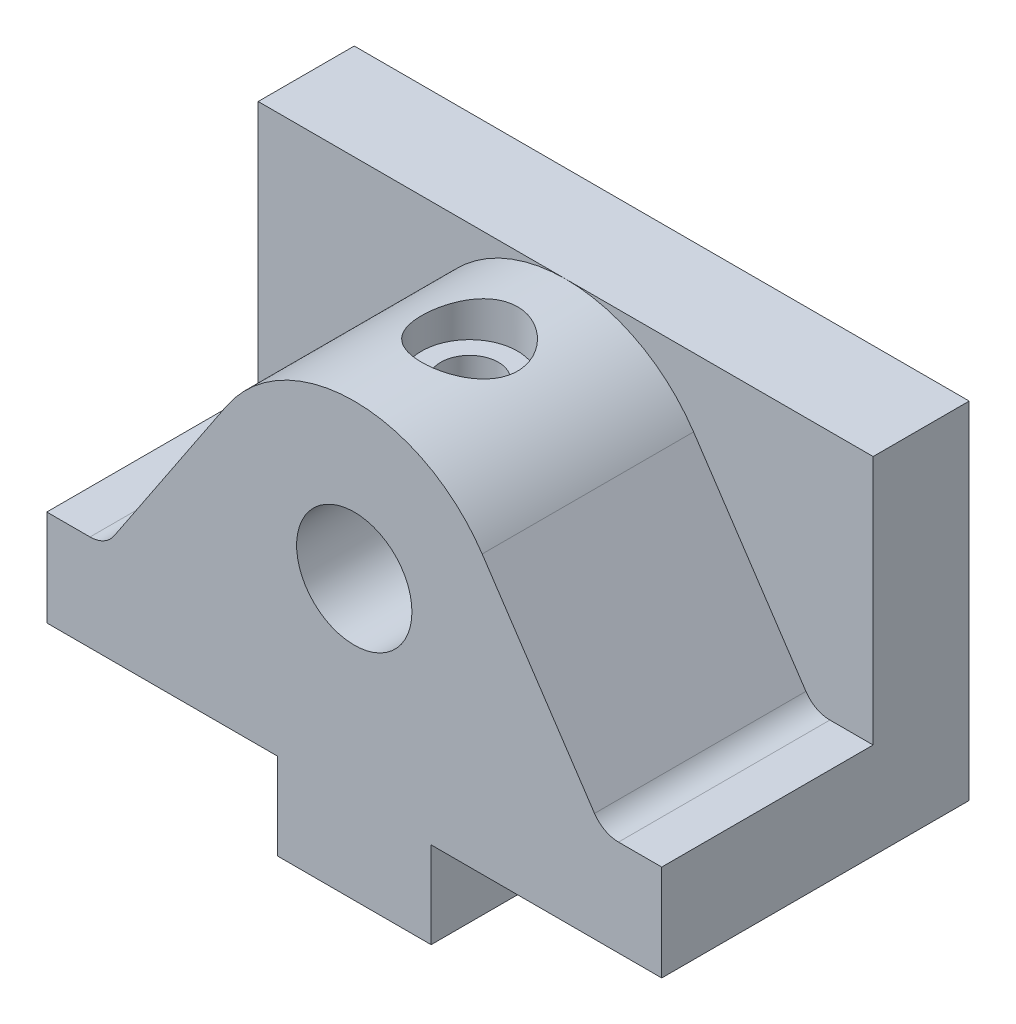
SolidWorks part; units mm, degrees
ref_plane "Front Plane" through (0, 0, 0) normal (0, 0, 1) x (1, 0, 0)
ref_plane "Top Plane" through (0, 0, 0) normal (0, 1, 0) x (1, 0, 0)
ref_plane "Right Plane" through (0, 0, 0) normal (1, 0, 0) x (0, 0, -1)
sketch "Sketch2" plane through (0, 0, 0) normal (0, 0, 1) x (1, 0, 0)
  line L0 (-32, 26) -> (32, 26) construction
  line L3 (0, 52) -> (0, 0) construction
  line L5 (-32, 16) -> (32, 16)
  line L6 (-8, 16) -> (-8, 7)
  line L7 (-8, 7) -> (8, 7)
  line L8 (-32, 0) -> (32, 0)
  line L9 (32, 0) -> (32, 52)
  line L10 (32, 52) -> (-32, 52)
  line L11 (-32, 52) -> (-32, 0)
  line L12 (-13.3134, 44.8742) -> (-25.0037, 27.3361)
  line L13 (-32, 26) -> (32, 26) construction
  line L14 (-32, 36) -> (32, 36) construction
  line L17 (8, 7) -> (8, 16)
  line L18 (13.3134, 44.8742) -> (25.0037, 27.3361)
  line L19 (-27.5, 26) -> (-32, 26)
  line L20 (27.5, 26) -> (32, 26)
  arc A1 (-13.3134, 44.8742) -> (13.3134, 44.8742) centre (0, 36) cw
  circle A3 centre (0, 36) radius 6
  arc A4 (-25.0037, 27.3361) -> (-27.5, 26) centre (-27.5, 29) cw
  arc A5 (25.0037, 27.3361) -> (27.5, 26) centre (27.5, 29) ccw
  point P30 (0, 26)
  dimension "D4" = 16
  dimension "D5" = 3
  dimension "D6" = 55
  dimension "D7" = 10
  dimension "D11" = 12
  dimension "D2" = 3
  dimension "D3" = 16
  dimension "D9" = 16
  dimension "D10" = 9
  dimension "D12" = 52
  dimension "D13" = 64
extrude "Boss-Extrude1" add sketch "Sketch2" along normal blind 22 contours A5 L18 A1 L12 A4 L19 L11 L5 L9 L20 A3 | L7 L17 L5 L6 region at (0, 29.4355, 0) region at (0, 11.5, 0)
extrude "Boss-Extrude2" add sketch "Sketch2<9>" against normal blind 10 contours L18 A5 L20 L9 L10 A1 | A5 L18 A1 L12 A4 L19 L11 L5 L9 L20 A3 | A4 L12 A1 L10 L11 L19 | A3 region at (0, 29.4355, 0) region at (-23.3107, 41.8121, 0) region at (23.3107, 41.8121, 0) region at (0, 36, 0)
sketch "Sketch2<9>" plane through (0, 0, 0) normal (0, 0, 1) x (1, 0, 0) same geometry as "Sketch2"
sketch "Sketch3" plane through (0, 0, 0) normal (0, 0, 1) x (1, 0, 0)
  circle A1 centre (0, 36) radius 6
  circle A2 centre (0, 36) radius 6
  dimension "D1" = 0
extrude "Cut-Extrude1" cut sketch "Sketch3" against normal blind 2 contours A2
sketch "Sketch5" plane through (0, 0, 0) normal (0, 0, -1) x (-1, 0, 0)
  line L4 (8, 7) -> (8, 16)
  line L5 (8, 16) -> (-8, 16)
  line L6 (-8, 16) -> (-8, 7)
  line L7 (-8, 7) -> (8, 7)
  line L8 (8, 7) -> (8, 16)
  line L9 (8, 16) -> (-8, 16)
  line L10 (-8, 16) -> (-8, 7)
  line L11 (-8, 7) -> (8, 7)
  dimension "D1" = 0
extrude "Boss-Extrude3" add sketch "Sketch5" along normal up to surface (10 mm away) up to face at (0, 34, -10)
sketch "Sketch4" plane through (0, 7, 0) normal (0, -1, 0) x (1, 0, 0)
  line L0 (0, 22) -> (0, -10) construction
  line L4 (-8, -10) -> (8, -10)
  line L5 (8, -10) -> (8, 22)
  line L6 (8, 22) -> (-8, 22)
  line L7 (-8, 22) -> (-8, -10)
  line L9 (8, -10) -> (8, 22)
  line L10 (8, 22) -> (-8, 22)
  line L11 (-8, 22) -> (-8, -10)
  line L12 (-8, -10) -> (8, -10)
  point P2 (0, 14)
  point P4 (0, -2)
  dimension "D2" = 8
  dimension "D3" = 16
  dimension "D1" = 0
hole_wizard "M6x1.0 Tapped Hole1" positions "3DSketch1" profile "Sketch6" tap size "M6x1.0" standard "ANSI Metric"
sketch3d "3DSketch1"
  line L0 (0, 7, 22) -> (0, 7, -10) construction
  point P0 (0, 7, 14)
  point P7 (0, 7, -2)
sketch "Sketch6" plane through (0, 7, 14) normal (1, 0, 0) x (0, 0, -1)
  line L0 (0, 0) -> (0, 17.7321)
  line L1 (0, 17.7321) -> (3, 16)
  line L2 (3, 16) -> (3, 0.025)
  line L3 (3, 0.025) -> (3.025, 0)
  line L5 (3.025, 0) -> (0, 0)
  line L6 (-3, 0.025) -> (-3.025, 0) construction
  line L10 (0, 17.7321) -> (-3, 16) construction
  line L11 (0, -6.35) -> (0, 107.95) construction
  dimension "Tap Drill Dia." = 6
  dimension "Tap Drill Depth" = 16
  dimension "Near C'Sink Dia." = 6.05
  dimension "Near C'Sink Angle" = 90
  dimension "Drill Angle" = 120
cosmetic thread "Hole Thread1" parameters "D1"=12, "D2"=6
cosmetic thread "Hole Thread2" parameters "D1"=12, "D2"=6
sketch "Sketch12" plane through (0, 52, 0) normal (0, 1, 0) x (1, 0, 0)
  line L0 (0, -22) -> (0, 10) construction
  line L1 (32, 10) -> (-32, 10) construction
  circle A0 centre (0, -10) radius 3
  dimension "D2" = 6
  dimension "D1" = 20
hole_wizard "Hole1" positions "3DSketch4" profile "Sketch14" legacy
sketch3d "3DSketch4"
  point P0 (0, 52, 10)
sketch "Sketch14" plane through (0, 52, 10) normal (1, 0, 0) x (0, 0, 1)
  line L0 (0, 0) -> (0, 15)
  line L1 (0, 15) -> (3, 15)
  line L2 (3, 15) -> (3, 4)
  line L3 (3, 4) -> (5, 4)
  line L4 (5, 4) -> (5, 0)
  line L5 (5, 0) -> (0, 0)
  line L6 (0, 110) -> (0, -10) construction
  dimension "Diameter" = 6
  dimension "Depth" = 15
  dimension "C-Bore Diameter" = 10
  dimension "C-Bore Depth" = 4
